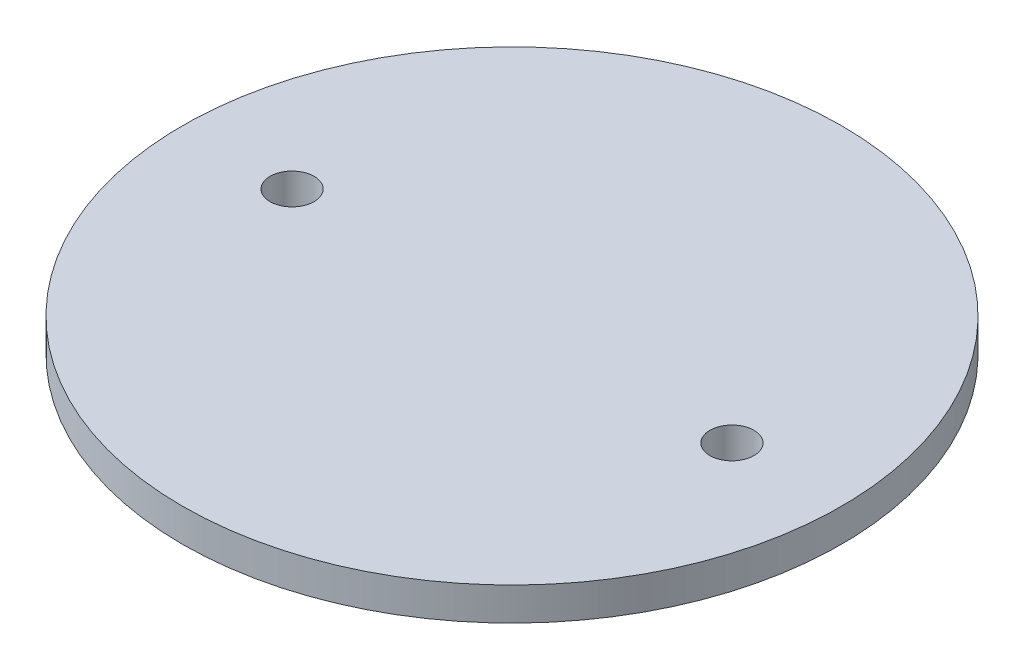
SolidWorks part; units mm, degrees
ref_plane "Front Plane" through (0, 0, 0) normal (0, 0, 1) x (1, 0, 0)
ref_plane "Top Plane" through (0, 0, 0) normal (0, 1, 0) x (1, 0, 0)
ref_plane "Right Plane" through (0, 0, 0) normal (1, 0, 0) x (0, 0, -1)
sketch "Sketch1" plane through (0, 0, 0) normal (0, 1, 0) x (1, 0, 0)
  circle A0 centre (0, 0) radius 47.575
  point P3 (0, 0)
  dimension "D1" = 95.15
extrude "Boss-Extrude1" add sketch "Sketch1" along normal blind 4.7625
sketch "Sketch2" plane through (0, 4.7625, 0) normal (0, 1, 0) x (1, 0, 0)
  circle A0 centre (31.75, 0) radius 3.175
  circle A1 centre (-31.75, 0) radius 3.175
  dimension "D1" = 6.35
  dimension "D2" = 6.35
  dimension "D3" = 31.75
  dimension "D4" = 31.75
extrude "Cut-Extrude1" cut sketch "Sketch2" against normal through all
